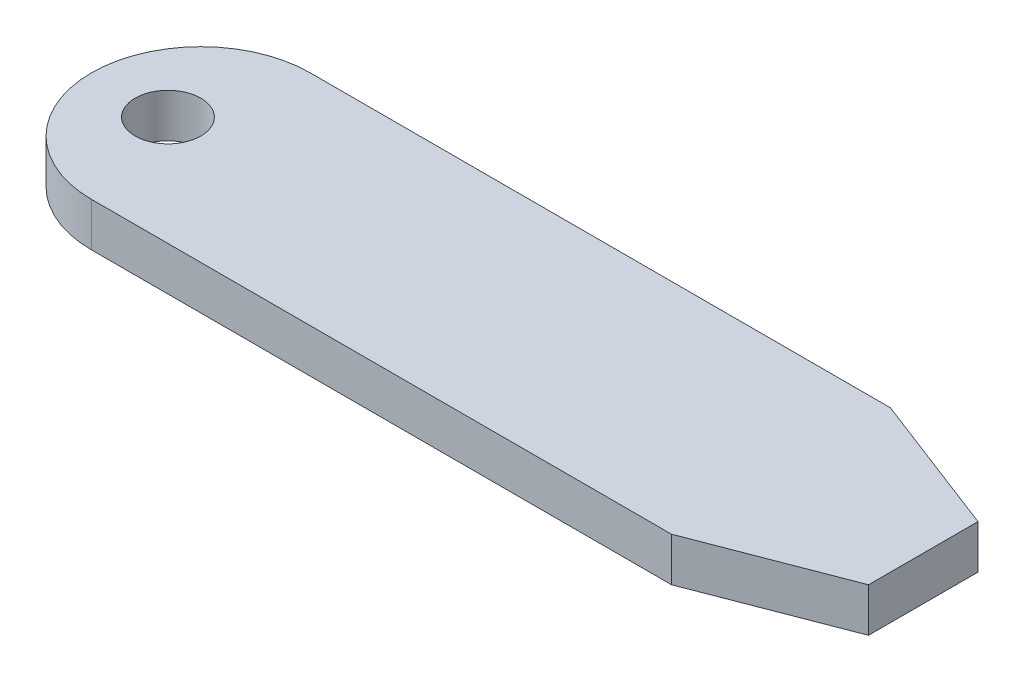
SolidWorks part; units mm, degrees
ref_plane "Alzado" through (0, 0, 0) normal (0, 0, 1) x (1, 0, 0)
ref_plane "Planta" through (0, 0, 0) normal (0, 1, 0) x (1, 0, 0)
ref_plane "Vista lateral" through (0, 0, 0) normal (1, 0, 0) x (0, 0, -1)
sketch "Croquis1" plane through (0, 0, 0) normal (0, 1, 0) x (1, 0, 0)
  line L0 (0, 0) -> (0, 26.7478) construction
  line L1 (0, 0) -> (43.7168, 0) construction
  line L2 (-13, 0) -> (-13, 5)
  line L3 (-13, 5) -> (0, 5)
  line L4 (0, 5) -> (18.5, 5)
  line L5 (25, 2.5) -> (25, 0)
  line L6 (25, 0) -> (25, -2.5)
  line L7 (18.5, -5) -> (0, -5)
  line L8 (0, -5) -> (-13, -5)
  line L9 (-13, -5) -> (-13, 0)
  line L10 (25, 2.5) -> (18.5, 5)
  line L11 (25, -2.5) -> (18.5, -5)
  circle A0 centre (-9.5, 0) radius 1.5
  dimension "D5" = 3.5
  dimension "D1" = 13
  dimension "D2" = 38
  dimension "D3" = 18.5
  dimension "D4" = 18.5
extrude "Saliente-Extruir1" add sketch "Croquis1" along normal blind 2
fillet "Redondeo1" radius 5 2 edges at (-13, 1, 5) (-13, 1, -5)
